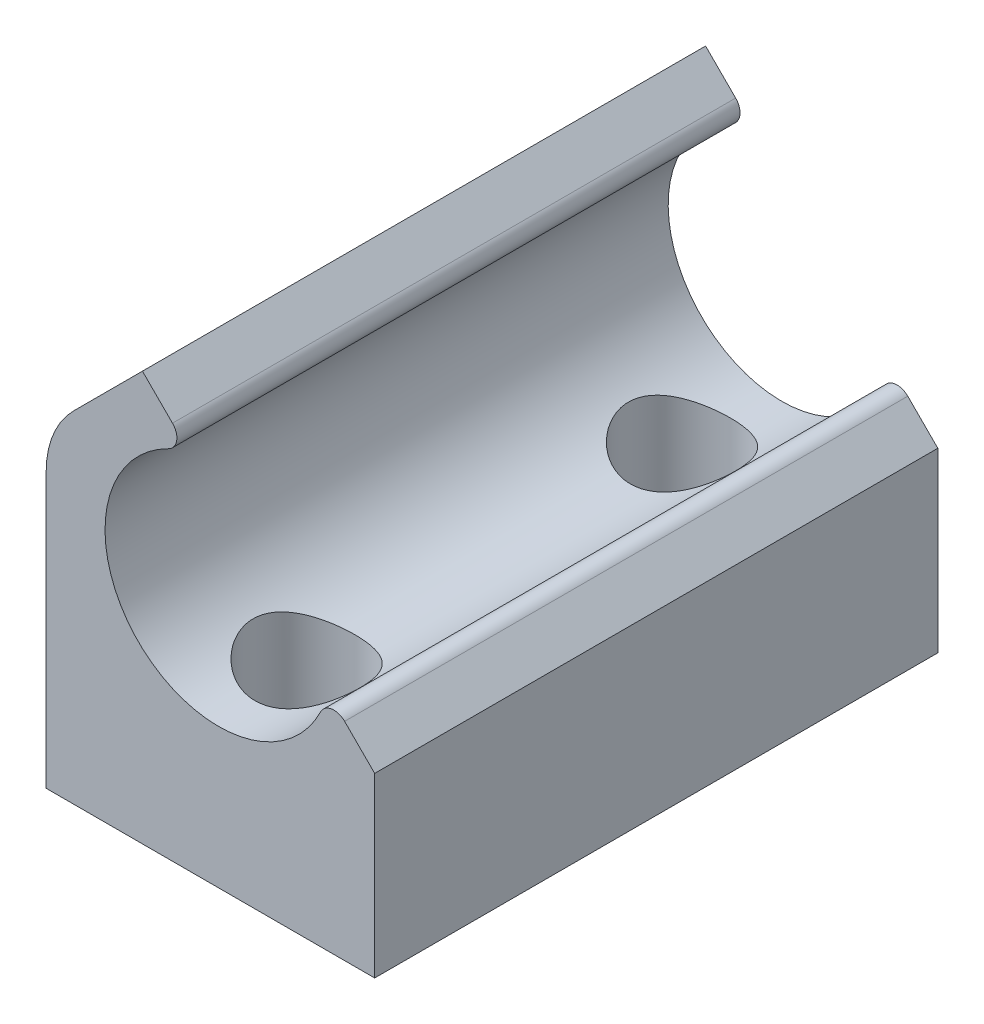
SolidWorks part; units mm, degrees
ref_plane "Front Plane" through (0, 0, 0) normal (0, 0, 1) x (1, 0, 0)
ref_plane "Top Plane" through (0, 0, 0) normal (0, 1, 0) x (1, 0, 0)
ref_plane "Right Plane" through (0, 0, 0) normal (1, 0, 0) x (0, 0, -1)
sketch "Sketch1" plane through (0, 0, 0) normal (0, 0, 1) x (1, 0, 0)
  line L0 (0, 0) -> (17.5, 0)
  line L1 (17.5, 0) -> (17.5, 9.44)
  line L2 (17.5, 9.44) -> (15.0251, 11.9149)
  line L3 (7.6032, 19.3368) -> (5.1283, 21.8117)
  line L4 (5.1283, 21.8117) -> (0, 16.6833)
  line L5 (0, 16.6833) -> (0, 0)
  arc A0 (15.0251, 11.9149) -> (7.6032, 19.3368) centre (9.1858, 13.4974) cw
  dimension "D1" = 6.05
  dimension "D2" = 3.5
  dimension "D3" = 17.5
  dimension "D4" = 9.44
  dimension "D5" = 3.01
  dimension "D6" = 45
extrude "Boss-Extrude1" add sketch "Sketch1" along normal blind 30
fillet "Fillet1" radius 0.8 2 edges at (15.0251, 11.9149, 15) (7.6032, 19.3368, 15)
ref_plane "Plane1" through (0, 10.8284, 0) normal (0, -1, 0) x (-1, 0, 0)
sketch "Sketch3" plane through (0, 10.8284, 0) normal (0, -1, 0) x (-1, 0, 0)
  line L0 (-3.1358, 0) -> (-14.6152, 0) construction
  line L1 (-3.1358, 0) -> (-14.6152, 0) construction
  circle A0 centre (-8.8755, -5) radius 2.85
  circle A1 centre (-8.8755, -25) radius 2.85
  point P7 (-8.8755, 0)
  dimension "D1" = 5.7
  dimension "D2" = 5
  dimension "D3" = 20
extrude "Cut-Extrude1" cut sketch "Sketch3" along normal blind 9
sketch "Sketch4" plane through (0, 10.8284, 0) normal (0, -1, 0) x (-1, 0, 0)
  circle A0 centre (-8.8755, -5) radius 1.55
  circle A1 centre (-8.8755, -25) radius 1.55
  dimension "D1" = 3.1
  dimension "D2" = 3.1
extrude "Cut-Extrude2" cut sketch "Sketch4" along normal through all
fillet "Fillet2" radius 5 1 edges at (0, 16.6833, 15)
